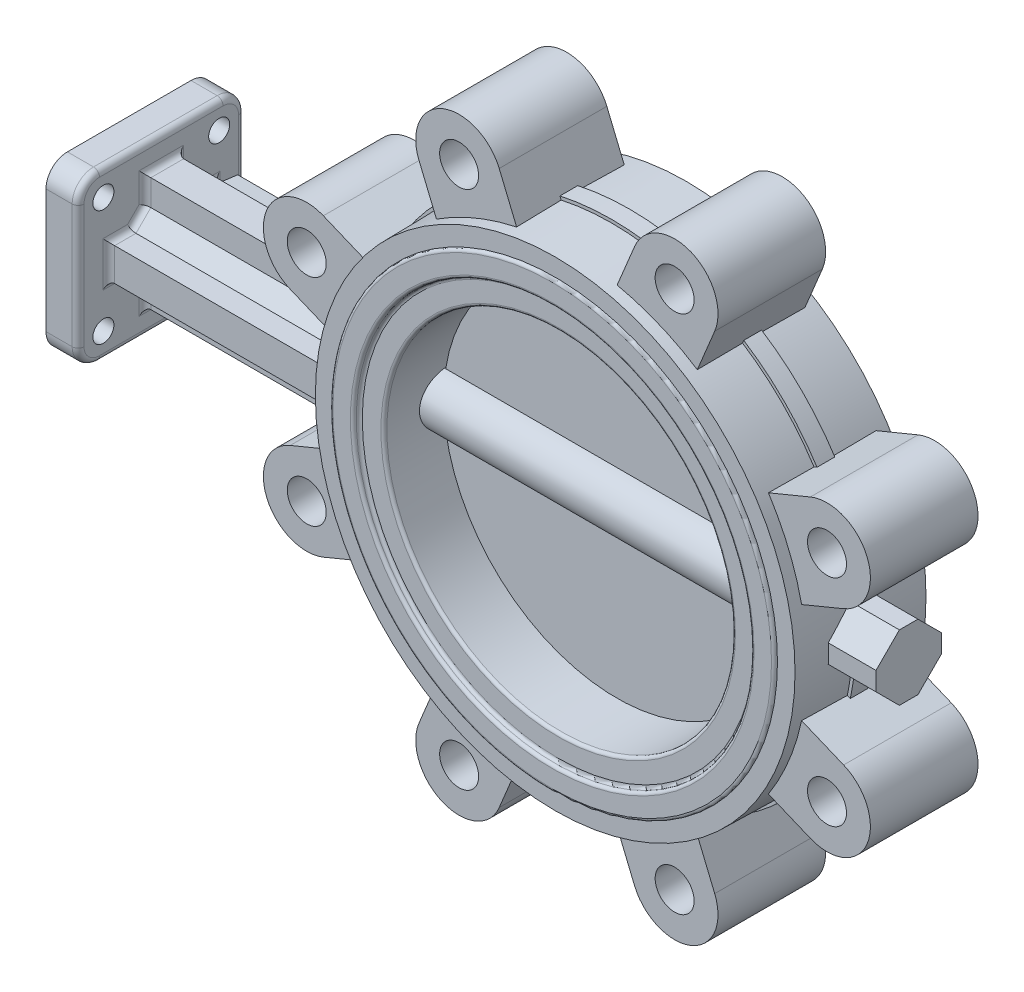
SolidWorks part; units mm, degrees
note: '?' marks a value the reader was unsure of.
material "A36"
ref_plane "Front Plane" through (0, 0, 0) normal (0, 0, 1) x (1, 0, 0)
ref_plane "Top Plane" through (0, 0, 0) normal (0, 1, 0) x (1, 0, 0)
ref_plane "Right Plane" through (0, 0, 0) normal (1, 0, 0) x (0, 0, -1)
sketch "Sketch1" plane through (0, 0, 0) normal (0, 0, 1) x (1, 0, 0)
  circle A0 centre (0, 0) radius 103
  dimension "D1" = 206.0001
extrude "Boss-Extrude1" add sketch "Sketch1" along normal mid plane 55.9816 draft 1
sketch "Sketch2" plane through (0, 0, 27.9908) normal (0, 0, 1) x (1, 0, 0)
  circle A0 centre (0, 0) radius 95
  dimension "D1" = 190
extrude "Boss-Extrude2" add sketch "Sketch2" along normal blind 1.27
sketch "Sketch3" plane through (0, 0, -27.9908) normal (0, 0, -1) x (-1, 0, 0)
  circle A0 centre (0, 0) radius 95
  circle A1 centre (0, 0) radius 95 construction
extrude "Boss-Extrude3" add sketch "Sketch3" along normal blind 1.27
sketch "Sketch5" plane through (0, 0, 29.2608) normal (0, 0, 1) x (1, 0, 0)
  circle A0 centre (0, 0) radius 85
  dimension "D1" = 170
extrude "Cut-Extrude2" cut sketch "Sketch5" against normal blind 2.54
sketch "Sketch4" plane through (0, 0, -29.2608) normal (0, 0, -1) x (-1, 0, 0)
  circle A0 centre (0, 0) radius 85
  circle A1 centre (0, 0) radius 85 construction
extrude "Cut-Extrude1" cut sketch "Sketch4" against normal blind 2.54
sketch "Sketch6" plane through (0, 0, 26.7208) normal (0, 0, 1) x (1, 0, 0)
  circle A0 centre (0, 0) radius 74.5
  dimension "D1" = 149
extrude "Cut-Extrude3" cut sketch "Sketch6" against normal through all both and the other way through all
sketch "Sketch7" plane through (0, 0, 0) normal (0, 1, 0) x (1, 0, 0)
  line L1 (-104.2895, 3.81) -> (-97.9395, 3.81)
  line L2 (-104.2895, 3.81) -> (-104.2895, -3.81)
  line L3 (-104.2895, -3.81) -> (-97.9395, -3.81)
  line L4 (-97.9395, 3.81) -> (-97.9395, -3.81)
  line L5 (-104.2895, 0) -> (-103, 0) construction
  line L7 (0, 0) -> (0, 27.9908) construction
  line L8 (102.5115, 27.9908) -> (-102.5115, 27.9908) construction
  dimension "D1" = 7.62
  dimension "D2" = 1.778
  dimension "D3" = 6.35
revolve "Revolve1" add sketch "Sketch7" angle 360 about L7
ref_plane "Plane1" through (104.2895, 0, 0) normal (1, 0, 0) x (0, 0, -1)
sketch "Sketch8" plane through (104.2895, 0, 0) normal (1, 0, 0) x (0, 0, -1)
  line L1 (-13.97, 13.97) -> (13.97, 13.97)
  line L2 (-13.97, 13.97) -> (-13.97, -13.97)
  line L3 (-13.97, -13.97) -> (13.97, -13.97)
  line L4 (13.97, 13.97) -> (13.97, -13.97)
  line L5 (-13.97, 13.97) -> (13.97, -13.97) construction
  line L6 (-13.97, -13.97) -> (13.97, 13.97) construction
  point P0 (0, 0)
  dimension "D1" = 27.94
extrude "Boss-Extrude4" add sketch "Sketch8" along normal blind 18.796 and the other way blind 10
chamfer "Chamfer1" distance 10 angle 45 4 edges at (112.4438, 13.97, -13.97) (112.4438, -13.97, -13.97) (112.4438, -13.97, 13.97) (112.4438, 13.97, 13.97)
ref_plane "Plane2" through (-104.2895, 0, 0) normal (-1, 0, 0) x (0, 0, 1)
sketch "Sketch9" plane through (-104.2895, 0, 0) normal (-1, 0, 0) x (0, 0, 1)
  line L1 (-22.479, 7) -> (-7, 7)
  line L2 (-22.479, 7) -> (-22.479, -7)
  line L3 (-22.479, -7) -> (-7, -7)
  line L4 (22.479, 7) -> (22.479, -7)
  line L5 (-22.479, 7) -> (22.479, -7) construction
  line L6 (-22.479, -7) -> (22.479, 7) construction
  line L7 (-7, -24.4094) -> (7, -24.4094)
  line L8 (-7, -24.4094) -> (-7, -7)
  line L9 (-7, 24.4094) -> (7, 24.4094)
  line L10 (7, -24.4094) -> (7, -7)
  line L11 (-7, -24.4094) -> (7, 24.4094) construction
  line L12 (-7, 24.4094) -> (7, -24.4094) construction
  line L13 (7, 7) -> (22.479, 7)
  line L14 (-7, 7) -> (-7, 24.4094)
  line L15 (7, 7) -> (7, 24.4094)
  line L19 (7, -7) -> (22.479, -7)
  point P0 (0, 0)
  point P5 (0, 0)
  dimension "D1" = 44.958
  dimension "D2" = 48.8188
  dimension "D3" = 14
extrude "Boss-Extrude5" add sketch "Sketch9" along normal blind 92.0664 and the other way blind 12.7
sketch "Sketch11" plane through (-196.3559, 0, 0) normal (-1, 0, 0) x (0, 0, 1)
  line L1 (35.56, 35.56) -> (-35.56, 35.56)
  line L2 (35.56, 35.56) -> (35.56, -35.56)
  line L3 (35.56, -35.56) -> (-35.56, -35.56)
  line L4 (-35.56, 35.56) -> (-35.56, -35.56)
  line L5 (35.56, 35.56) -> (-35.56, -35.56) construction
  line L6 (35.56, -35.56) -> (-35.56, 35.56) construction
  point P0 (0, 0)
  dimension "D1" = 71.12
extrude "Boss-Extrude7" add sketch "Sketch11" along normal blind 13.716
chamfer "Chamfer2" distance 6.35 angle 45 4 edges at (-149.4976, 7, 7) (-149.4976, -7, 7) (-149.4976, -7, -7) (-149.4976, 7, -7)
fillet "Fillet1" radius 9.144 4 edges at (-203.2139, 35.56, -35.56) (-203.2139, 35.56, 35.56) (-203.2139, -35.56, -35.56) (-203.2139, -35.56, 35.56)
sketch "Sketch12" plane through (0, 0, -3.81) normal (0, 0, -1) x (-1, 0, 0)
  line L0 (196.3559, 26.416) -> (196.3559, -26.416) construction
  line L1 (187.4659, 15.875) -> (130.3159, 15.875)
  line L2 (187.4659, 15.875) -> (187.4659, -15.875)
  line L3 (187.4659, -15.875) -> (130.3159, -15.875)
  line L4 (130.3159, 15.875) -> (130.3159, -15.875)
  line L5 (187.4659, 15.875) -> (130.3159, -15.875) construction
  line L6 (187.4659, -15.875) -> (130.3159, 15.875) construction
  line L7 (158.8909, 0) -> (0, 0) construction
  point P0 (158.8909, 0)
  dimension "D1" = 57.15
  dimension "D2" = 31.75
  dimension "D3" = 8.89
extrude "Boss-Extrude8" add sketch "Sketch12" along normal up to surface (18.669 mm away) draft 4
fillet "Fillet2" radius 1.27 8 edges at (85, 0, 26.7208) (74.5, 0, 26.7208) (-74.5, 0, -26.7208) (95, 0, 29.2608) (85, 0, 29.2608) (-95, 0, -29.2608) (-85, 0, -29.2608) (-85, 0, -26.7208)
sketch "Sketch14" plane through (-210.0719, 0, 0) normal (-1, 0, 0) x (0, 0, 1)
  circle A0 centre (0, 0) radius 11.5062
  dimension "D1" = 23.0124
extrude "Cut-Extrude5" cut sketch "Sketch14" against normal blind 7.62
hole_wizard "M8 Clearance Hole1" positions "Sketch16" profile "Sketch17" hole size "M8" standard "ANSI Metric"
sketch "Sketch16" plane through (-210.0719, 0, 0) normal (-1, 0, 0) x (0, 0, 1)
  line L1 (-24.7487, 24.7487) -> (24.7487, 24.7487)
  line L2 (-24.7487, 24.7487) -> (-24.7487, -24.7487)
  line L3 (-24.7487, -24.7487) -> (24.7487, -24.7487)
  line L4 (24.7487, 24.7487) -> (24.7487, -24.7487)
  line L5 (0, 0) -> (0, 24.7487)
  line L6 (0, 0) -> (0, -24.7487)
  point P0 (-24.7487, 24.7487)
  point P2 (24.7487, 24.7487)
  point P4 (24.7487, -24.7487)
  point P6 (-24.7487, -24.7487)
  dimension "D1" = 70
sketch "Sketch17" plane through (-210.0719, 24.7487, -24.7487) normal (0, 1, 0) x (0, 0, 1)
  line L0 (0, 0) -> (0, 13.716)
  line L1 (0, 13.716) -> (4.5, 13.716)
  line L2 (4.5, 13.716) -> (4.5, 0)
  line L5 (4.5, 0) -> (0, 0)
  line L11 (0, -6.35) -> (0, 107.95) construction
  dimension "Thru Hole Dia." = 9
  dimension "Thru Hole Depth" = 13.716
sketch "Sketch18" plane through (123.0855, 0, 0) normal (1, 0, 0) x (0, 0, -1)
  circle A0 centre (0, 0) radius 11.5
  dimension "D1" = 23
extrude "Boss-Extrude9" add sketch "Sketch18" against normal blind 211.328
sketch "Sketch19" plane through (-202.4519, 0, 0) normal (-1, 0, 0) x (0, 0, 1)
  circle A0 centre (0, 0) radius 9.0043
  dimension "D1" = 18.0086
extrude "Boss-Extrude10" add sketch "Sketch19" along normal offset from surface (6.62 mm away) 1 up to face at (-210.0719, 0, 11.5062)
sketch "Sketch20" plane through (-209.0719, 0, 0) normal (-1, 0, 0) x (0, 0, 1)
  line L0 (0, 9.8783) -> (-9.8783, 0)
  line L5 (0, -9.8783) -> (9.8783, 0)
  line L6 (9.8783, 0) -> (0, 9.8783)
  line L7 (-9.8783, 0) -> (0, -9.8783)
  line L8 (-9.8783, 0) -> (9.8783, 0) construction
  line L9 (0, 9.8783) -> (0, -9.8783) construction
  point P4 (0, 0)
  dimension "D1" = 13.97
  dimension "D2" = 90
extrude "Boss-Extrude11" add sketch "Sketch20" along normal blind 19.5
chamfer "Chamfer3" distance 1.5 angle 45 4 edges at (-218.8219, -9.8783, 0) (-218.8219, 0, 9.8783) (-218.8219, 9.8783, 0) (-218.8219, 0, -9.8783)
sketch "Sketch21" plane through (0, 0, 0) normal (0, 0, 1) x (1, 0, 0)
  circle A2 centre (0, 0) radius 74
  dimension "D2" = 148
extrude "Boss-Extrude12" add sketch "Sketch21" along normal mid plane 3.33
sketch "Sketch22" plane through (0, 0, 0) normal (0, 0, 1) x (1, 0, 0)
  line L1 (0, 0) -> (-111.1845, 46.0541) construction
  line L2 (-74.1441, 0) -> (-210.0719, 0) construction
  line L4 (0, 0) -> (-48.4526, 0) construction
  line L5 (-210.0719, -26.416) -> (-210.0719, 26.416) construction
  line L7 (-104.0888, 63.1847) -> (-86.0504, 55.713)
  line L8 (-118.2802, 28.9235) -> (-100.2418, 21.4518)
  circle A4 centre (0, 0) radius 102.5115 construction
  arc A8 (-104.0888, 63.1847) -> (-118.2802, 28.9235) centre (-111.1845, 46.0541) ccw
  arc A9 (-86.0504, 55.713) -> (-100.2418, 21.4518) centre (0, 0) ccw
  dimension "D2" = 18.542
  dimension "D1" = 22.5
  dimension "D5" = 120.3452
extrude "Boss-Extrude13" add sketch "Sketch22" along normal mid plane 46
pattern_circular "CirPattern1" count 8 over 360 about axis through (0, 0, 0) along (0, 0, 1) of "Boss-Extrude13"
hole_wizard "3/4-10 Tapped Hole1" positions "Sketch23" profile "Sketch24" tap size "3/4-10" standard "ANSI Inch" end condition through all
sketch "Sketch23" plane through (0, 0, 23) normal (0, 0, 1) x (1, 0, 0)
  point P0 (-46.0541, 111.1845)
  point P3 (-111.1845, 46.0541)
  point P6 (111.1845, 46.0541)
  point P9 (46.0541, 111.1845)
  point P12 (111.1845, -46.0541)
  point P15 (46.0541, -111.1845)
  point P18 (-46.0541, -111.1845)
  point P21 (-111.1845, -46.0541)
  dimension "D1" = 120.3452
sketch "Sketch24" plane through (-46.0541, 111.1845, 23) normal (1, 0, 0) x (0, -1, 0)
  line L0 (0, 0) -> (0, 58.56)
  line L1 (0, 58.56) -> (8.3337, 58.56)
  line L2 (8.3337, 58.56) -> (8.3337, 0)
  line L5 (8.3337, 0) -> (0, 0)
  line L11 (0, -6.35) -> (0, 107.95) construction
  dimension "Thru Tap Drill Dia." = 16.6675
  dimension "Thru Tap Drill Depth" = 58.56
cosmetic thread "Hole Thread1" parameters "D2"=19.05
cosmetic thread "Hole Thread2" parameters "D2"=19.05
cosmetic thread "Hole Thread3" parameters "D2"=19.05
cosmetic thread "Hole Thread4" parameters "D2"=19.05
cosmetic thread "Hole Thread5" parameters "D2"=19.05
cosmetic thread "Hole Thread6" parameters "D2"=19.05
cosmetic thread "Hole Thread7" parameters "D2"=19.05
cosmetic thread "Hole Thread8" parameters "D2"=19.05
fillet "Fillet3" radius 2.54 24 edges at (-196.3559, -32.8818, 32.8818) (-196.3559, -35.56, 0) (-196.3559, -32.8818, -32.8818) (-196.3559, 0, -35.56) (-196.3559, 32.8818, -32.8818) (-196.3559, 35.56, 0) (-196.3559, 32.8818, 32.8818) (-196.3559, 7, 17.9145) (-196.3559, 24.4094, 0) (-196.3559, 10.175, -10.175) (-196.3559, 7, -17.9145) (-196.3559, 0, -22.479) (-196.3559, -7, -17.9145) (-196.3559, -10.175, -10.175) (-196.3559, -24.4094, 0) (-196.3559, -7, 17.9145) (-196.3559, 10.175, 10.175) (-196.3559, 0, 22.479) (-196.3559, -10.175, 10.175) (-196.3559, 0, 35.56) (-196.3559, -18.8797, -7) (-196.3559, -18.8797, 7) (-196.3559, 18.8797, 7) (-196.3559, 18.8797, -7)
ref_axis "Axis1" through (0, 0, -25.4508) along (0, 0, 1)?
ref_point "Point1"
ref_point "Point2"
ref_plane "Plane3" through (0, 0, 0) normal (1, 0, 0) x (0, 0, -1)
